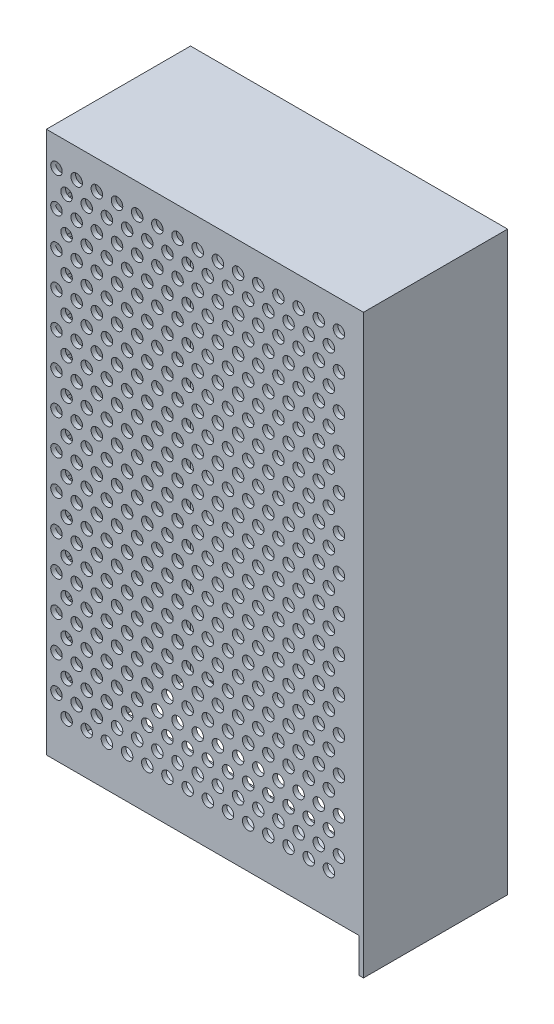
SolidWorks part; units mm, degrees
material "1060 Alloy"
ref_plane "Front Plane" through (0, 0, 0) normal (0, 0, 1) x (1, 0, 0)
ref_plane "Top Plane" through (0, 0, 0) normal (0, 1, 0) x (1, 0, 0)
ref_plane "Right Plane" through (0, 0, 0) normal (1, 0, 0) x (0, 0, -1)
sketch "Sketch1" plane through (0, 0, 0) normal (0, 0, 1) x (1, 0, 0)
  line L0 (-55, 0) -> (0, 0) construction
  line L1 (-55, 100) -> (55, 100)
  line L2 (-55, 100) -> (-55, -100)
  line L3 (-55, -100) -> (55, -100)
  line L4 (55, 100) -> (55, -100)
  line L5 (0, 0) -> (55, 0) construction
  dimension "D1" = 110
  dimension "D2" = 200
extrude "Boss-Extrude1" add sketch "Sketch1" along normal blind 50
shell "Shell1" thickness 1.6
sketch "Sketch2" plane through (0, 0, 50) normal (0, 0, 1) x (1, 0, 0)
  line L0 (-55, -100) -> (55, -100) construction
  line L1 (-53.4, -100) -> (53.4, -100)
  line L2 (-53.4, -100) -> (-53.4, -88) construction
  line L3 (-53.4, -88) -> (53.4, -88)
  line L4 (53.4, -100) -> (53.4, -88)
  line L5 (-53.4, -94) -> (-55, -94) construction
  line L6 (-55, 100) -> (-55, -100) construction
  line L7 (53.4, -94) -> (55, -94) construction
  line L8 (55, -100) -> (55, 100) construction
  line L9 (-53.4, -88) -> (-55, -88)
  line L10 (-55, -88) -> (-55, -100)
  line L11 (-55, -100) -> (-53.4, -100)
  dimension "D1" = 1.6
  dimension "D2" = 12
extrude "Cut-Extrude1" cut sketch "Sketch2" against normal up to surface (48.4 mm away) up to face at (0, -0.8, 1.6)
sketch "Sketch3" plane through (0, 0, 50) normal (0, 0, 1) x (1, 0, 0)
  line L0 (-55, 100) -> (-55, -88) construction
  line L1 (-55, -88) -> (55, -88)
  line L2 (-55, -88) -> (-55, -86.4)
  line L3 (-55, -86.4) -> (55, -86.4)
  line L4 (55, -88) -> (55, -86.4)
  line L5 (55, -100) -> (55, 100) construction
  line L6 (53.4, -88) -> (-55, -88) construction
  dimension "D1" = 1.6
extrude "Boss-Extrude2" add sketch "Sketch3" against normal blind 25
sketch "Sketch4" plane through (0, 0, 50) normal (0, 0, 1) x (1, 0, 0)
  line L0 (-55, 100) -> (-55, -88) construction
  line L1 (-42.5, 77.5) -> (7.5, 77.5) construction
  line L2 (-42.5, 77.5) -> (-42.5, 27.5) construction
  line L3 (-42.5, 27.5) -> (7.5, 27.5) construction
  line L4 (7.5, 77.5) -> (7.5, 27.5) construction
  line L5 (55, 100) -> (-55, 100) construction
  line L6 (-17.5, 77.5) -> (-17.5, 52.5) construction
  line L7 (-17.5, 52.5) -> (-17.5, 27.5) construction
  circle A0 centre (-17.5, 52.5) radius 29
  circle A1 centre (-42.5, 77.5) radius 1.5
  circle A2 centre (7.5, 27.5) radius 1.5
  dimension "D1" = 3
  dimension "D2" = 12.5
  dimension "D5" = 58
  dimension "D3" = 22.5
  dimension "D4" = 50
extrude "Cut-Extrude2" [suppressed] cut sketch "Sketch4" against normal up to surface (48.4 mm away)
sketch "Sketch5" plane through (0, 0, 0) normal (0, 0, -1) x (-1, 0, 0)
  line L0 (-55, 100) -> (55, 100) construction
  line L1 (-46, 90) -> (46, 90) construction
  line L2 (-46, 90) -> (-46, -87) construction
  line L3 (-46, -87) -> (46, -87) construction
  line L4 (46, 90) -> (46, -87) construction
  line L5 (-55, -100) -> (-55, 100) construction
  line L6 (55, 100) -> (55, -100) construction
  line L7 (55, -100) -> (-55, -100) construction
  circle A0 centre (-46, 90) radius 1.5
  circle A1 centre (46, 90) radius 1.5
  circle A2 centre (-46, -87) radius 1.5
  circle A3 centre (46, -87) radius 1.5
  dimension "D6" = 3
  dimension "D1" = 10
  dimension "D2" = 9
  dimension "D3" = 9
  dimension "D4" = 177
  dimension "D5" = 13
extrude "Cut-Extrude3" cut sketch "Sketch5" against normal up to surface (1.6 mm away) up to face at (-18.3333, -29.8667, 1.6)
sketch "Sketch6" plane through (0, 0, 50) normal (0, 0, 1) x (1, 0, 0)
  line L0 (55, 100) -> (-55, 100) construction
  line L2 (-55, 100) -> (-55, -88) construction
  line L3 (-51.5, 90) -> (-44.5, 90) construction
  line L4 (-48, 90) -> (-48, 83.9378) construction
  line L5 (-51.5, 90) -> (-48, 83.9378) construction
  line L6 (-48, 83.9378) -> (-41, 83.9378) construction
  line L7 (-51.5, 77.8756) -> (-44.5, 77.8756) construction
  line L8 (-48, 77.8756) -> (-48, 71.8135) construction
  line L9 (-51.5, 77.8756) -> (-48, 71.8135) construction
  line L10 (-48, 71.8135) -> (-41, 71.8135) construction
  line L11 (-51.5, 65.7513) -> (-44.5, 65.7513) construction
  line L12 (-48, 65.7513) -> (-48, 59.6891) construction
  line L13 (-51.5, 65.7513) -> (-48, 59.6891) construction
  line L14 (-48, 59.6891) -> (-41, 59.6891) construction
  line L15 (-51.5, 53.6269) -> (-44.5, 53.6269) construction
  line L16 (-48, 53.6269) -> (-48, 47.5648) construction
  line L17 (-51.5, 53.6269) -> (-48, 47.5648) construction
  line L18 (-48, 47.5648) -> (-41, 47.5648) construction
  line L19 (-51.5, 41.5026) -> (-44.5, 41.5026) construction
  line L20 (-48, 41.5026) -> (-48, 35.4404) construction
  line L21 (-51.5, 41.5026) -> (-48, 35.4404) construction
  line L22 (-48, 35.4404) -> (-41, 35.4404) construction
  line L23 (-51.5, 29.3782) -> (-44.5, 29.3782) construction
  line L24 (-48, 29.3782) -> (-48, 23.316) construction
  line L25 (-51.5, 29.3782) -> (-48, 23.316) construction
  line L26 (-48, 23.316) -> (-41, 23.316) construction
  line L27 (-51.5, 17.2539) -> (-44.5, 17.2539) construction
  line L28 (-48, 17.2539) -> (-48, 11.1917) construction
  line L29 (-51.5, 17.2539) -> (-48, 11.1917) construction
  line L30 (-48, 11.1917) -> (-41, 11.1917) construction
  line L31 (-51.5, 5.1295) -> (-44.5, 5.1295) construction
  line L32 (-48, 5.1295) -> (-48, -0.9327) construction
  line L33 (-51.5, 5.1295) -> (-48, -0.9327) construction
  line L34 (-48, -0.9327) -> (-41, -0.9327) construction
  line L35 (-51.5, -6.9948) -> (-44.5, -6.9948) construction
  line L36 (-48, -6.9948) -> (-48, -13.057) construction
  line L37 (-51.5, -6.9948) -> (-48, -13.057) construction
  line L38 (-48, -13.057) -> (-41, -13.057) construction
  line L39 (-51.5, -19.1192) -> (-44.5, -19.1192) construction
  line L40 (-48, -19.1192) -> (-48, -25.1814) construction
  line L41 (-51.5, -19.1192) -> (-48, -25.1814) construction
  line L42 (-48, -25.1814) -> (-41, -25.1814) construction
  line L43 (-51.5, -31.2436) -> (-44.5, -31.2436) construction
  line L44 (-48, -31.2436) -> (-48, -37.3057) construction
  line L45 (-51.5, -31.2436) -> (-48, -37.3057) construction
  line L46 (-48, -37.3057) -> (-41, -37.3057) construction
  line L47 (-51.5, -43.3679) -> (-44.5, -43.3679) construction
  line L48 (-48, -43.3679) -> (-48, -49.4301) construction
  line L49 (-51.5, -43.3679) -> (-48, -49.4301) construction
  line L50 (-48, -49.4301) -> (-41, -49.4301) construction
  line L51 (-51.5, -55.4923) -> (-44.5, -55.4923) construction
  line L52 (-48, -55.4923) -> (-48, -61.5544) construction
  line L53 (-51.5, -55.4923) -> (-48, -61.5544) construction
  line L54 (-48, -61.5544) -> (-41, -61.5544) construction
  line L55 (-51.5, -67.6166) -> (-44.5, -67.6166) construction
  line L56 (-48, -67.6166) -> (-48, -73.6788) construction
  line L57 (-51.5, -67.6166) -> (-48, -73.6788) construction
  line L58 (-48, -73.6788) -> (-41, -73.6788) construction
  line L67 (-48, 83.9378) -> (-51.5, 77.8756) construction
  line L68 (-48, 83.9378) -> (-48, 77.8756) construction
  circle A0 centre (-51.5, 90) radius 2
  circle A1 centre (-44.5, 90) radius 2
  circle A2 centre (-37.5, 90) radius 2
  circle A3 centre (-30.5, 90) radius 2
  circle A4 centre (-23.5, 90) radius 2
  circle A5 centre (-16.5, 90) radius 2
  circle A6 centre (-9.5, 90) radius 2
  circle A7 centre (-2.5, 90) radius 2
  circle A8 centre (4.5, 90) radius 2
  circle A9 centre (11.5, 90) radius 2
  circle A10 centre (18.5, 90) radius 2
  circle A11 centre (25.5, 90) radius 2
  circle A12 centre (32.5, 90) radius 2
  circle A13 centre (39.5, 90) radius 2
  circle A14 centre (46.5, 90) radius 2
  circle A15 centre (-48, 83.9378) radius 2
  circle A16 centre (-41, 83.9378) radius 2
  circle A17 centre (-34, 83.9378) radius 2
  circle A18 centre (-27, 83.9378) radius 2
  circle A19 centre (-20, 83.9378) radius 2
  circle A20 centre (-13, 83.9378) radius 2
  circle A21 centre (-6, 83.9378) radius 2
  circle A22 centre (1, 83.9378) radius 2
  circle A23 centre (8, 83.9378) radius 2
  circle A24 centre (15, 83.9378) radius 2
  circle A25 centre (22, 83.9378) radius 2
  circle A26 centre (29, 83.9378) radius 2
  circle A27 centre (36, 83.9378) radius 2
  circle A28 centre (43, 83.9378) radius 2
  circle A29 centre (-51.5, 77.8756) radius 2
  circle A30 centre (-44.5, 77.8756) radius 2
  circle A31 centre (-37.5, 77.8756) radius 2
  circle A32 centre (-30.5, 77.8756) radius 2
  circle A33 centre (-23.5, 77.8756) radius 2
  circle A34 centre (-16.5, 77.8756) radius 2
  circle A35 centre (-9.5, 77.8756) radius 2
  circle A36 centre (-2.5, 77.8756) radius 2
  circle A37 centre (4.5, 77.8756) radius 2
  circle A38 centre (11.5, 77.8756) radius 2
  circle A39 centre (18.5, 77.8756) radius 2
  circle A40 centre (25.5, 77.8756) radius 2
  circle A41 centre (32.5, 77.8756) radius 2
  circle A42 centre (39.5, 77.8756) radius 2
  circle A43 centre (46.5, 77.8756) radius 2
  circle A44 centre (-48, 71.8135) radius 2
  circle A45 centre (-41, 71.8135) radius 2
  circle A46 centre (-34, 71.8135) radius 2
  circle A47 centre (-27, 71.8135) radius 2
  circle A48 centre (-20, 71.8135) radius 2
  circle A49 centre (-13, 71.8135) radius 2
  circle A50 centre (-6, 71.8135) radius 2
  circle A51 centre (1, 71.8135) radius 2
  circle A52 centre (8, 71.8135) radius 2
  circle A53 centre (15, 71.8135) radius 2
  circle A54 centre (22, 71.8135) radius 2
  circle A55 centre (29, 71.8135) radius 2
  circle A56 centre (36, 71.8135) radius 2
  circle A57 centre (43, 71.8135) radius 2
  circle A58 centre (-51.5, 65.7513) radius 2
  circle A59 centre (-44.5, 65.7513) radius 2
  circle A60 centre (-37.5, 65.7513) radius 2
  circle A61 centre (-30.5, 65.7513) radius 2
  circle A62 centre (-23.5, 65.7513) radius 2
  circle A63 centre (-16.5, 65.7513) radius 2
  circle A64 centre (-9.5, 65.7513) radius 2
  circle A65 centre (-2.5, 65.7513) radius 2
  circle A66 centre (4.5, 65.7513) radius 2
  circle A67 centre (11.5, 65.7513) radius 2
  circle A68 centre (18.5, 65.7513) radius 2
  circle A69 centre (25.5, 65.7513) radius 2
  circle A70 centre (32.5, 65.7513) radius 2
  circle A71 centre (39.5, 65.7513) radius 2
  circle A72 centre (46.5, 65.7513) radius 2
  circle A73 centre (-48, 59.6891) radius 2
  circle A74 centre (-41, 59.6891) radius 2
  circle A75 centre (-34, 59.6891) radius 2
  circle A76 centre (-27, 59.6891) radius 2
  circle A77 centre (-20, 59.6891) radius 2
  circle A78 centre (-13, 59.6891) radius 2
  circle A79 centre (-6, 59.6891) radius 2
  circle A80 centre (1, 59.6891) radius 2
  circle A81 centre (8, 59.6891) radius 2
  circle A82 centre (15, 59.6891) radius 2
  circle A83 centre (22, 59.6891) radius 2
  circle A84 centre (29, 59.6891) radius 2
  circle A85 centre (36, 59.6891) radius 2
  circle A86 centre (43, 59.6891) radius 2
  circle A87 centre (-51.5, 53.6269) radius 2
  circle A88 centre (-44.5, 53.6269) radius 2
  circle A89 centre (-37.5, 53.6269) radius 2
  circle A90 centre (-30.5, 53.6269) radius 2
  circle A91 centre (-23.5, 53.6269) radius 2
  circle A92 centre (-16.5, 53.6269) radius 2
  circle A93 centre (-9.5, 53.6269) radius 2
  circle A94 centre (-2.5, 53.6269) radius 2
  circle A95 centre (4.5, 53.6269) radius 2
  circle A96 centre (11.5, 53.6269) radius 2
  circle A97 centre (18.5, 53.6269) radius 2
  circle A98 centre (25.5, 53.6269) radius 2
  circle A99 centre (32.5, 53.6269) radius 2
  circle A100 centre (39.5, 53.6269) radius 2
  circle A101 centre (46.5, 53.6269) radius 2
  circle A102 centre (-48, 47.5648) radius 2
  circle A103 centre (-41, 47.5648) radius 2
  circle A104 centre (-34, 47.5648) radius 2
  circle A105 centre (-27, 47.5648) radius 2
  circle A106 centre (-20, 47.5648) radius 2
  circle A107 centre (-13, 47.5648) radius 2
  circle A108 centre (-6, 47.5648) radius 2
  circle A109 centre (1, 47.5648) radius 2
  circle A110 centre (8, 47.5648) radius 2
  circle A111 centre (15, 47.5648) radius 2
  circle A112 centre (22, 47.5648) radius 2
  circle A113 centre (29, 47.5648) radius 2
  circle A114 centre (36, 47.5648) radius 2
  circle A115 centre (43, 47.5648) radius 2
  circle A116 centre (-51.5, 41.5026) radius 2
  circle A117 centre (-44.5, 41.5026) radius 2
  circle A118 centre (-37.5, 41.5026) radius 2
  circle A119 centre (-30.5, 41.5026) radius 2
  circle A120 centre (-23.5, 41.5026) radius 2
  circle A121 centre (-16.5, 41.5026) radius 2
  circle A122 centre (-9.5, 41.5026) radius 2
  circle A123 centre (-2.5, 41.5026) radius 2
  circle A124 centre (4.5, 41.5026) radius 2
  circle A125 centre (11.5, 41.5026) radius 2
  circle A126 centre (18.5, 41.5026) radius 2
  circle A127 centre (25.5, 41.5026) radius 2
  circle A128 centre (32.5, 41.5026) radius 2
  circle A129 centre (39.5, 41.5026) radius 2
  circle A130 centre (46.5, 41.5026) radius 2
  circle A131 centre (-48, 35.4404) radius 2
  circle A132 centre (-41, 35.4404) radius 2
  circle A133 centre (-34, 35.4404) radius 2
  circle A134 centre (-27, 35.4404) radius 2
  circle A135 centre (-20, 35.4404) radius 2
  circle A136 centre (-13, 35.4404) radius 2
  circle A137 centre (-6, 35.4404) radius 2
  circle A138 centre (1, 35.4404) radius 2
  circle A139 centre (8, 35.4404) radius 2
  circle A140 centre (15, 35.4404) radius 2
  circle A141 centre (22, 35.4404) radius 2
  circle A142 centre (29, 35.4404) radius 2
  circle A143 centre (36, 35.4404) radius 2
  circle A144 centre (43, 35.4404) radius 2
  circle A145 centre (-51.5, 29.3782) radius 2
  circle A146 centre (-44.5, 29.3782) radius 2
  circle A147 centre (-37.5, 29.3782) radius 2
  circle A148 centre (-30.5, 29.3782) radius 2
  circle A149 centre (-23.5, 29.3782) radius 2
  circle A150 centre (-16.5, 29.3782) radius 2
  circle A151 centre (-9.5, 29.3782) radius 2
  circle A152 centre (-2.5, 29.3782) radius 2
  circle A153 centre (4.5, 29.3782) radius 2
  circle A154 centre (11.5, 29.3782) radius 2
  circle A155 centre (18.5, 29.3782) radius 2
  circle A156 centre (25.5, 29.3782) radius 2
  circle A157 centre (32.5, 29.3782) radius 2
  circle A158 centre (39.5, 29.3782) radius 2
  circle A159 centre (46.5, 29.3782) radius 2
  circle A160 centre (-48, 23.316) radius 2
  circle A161 centre (-41, 23.316) radius 2
  circle A162 centre (-34, 23.316) radius 2
  circle A163 centre (-27, 23.316) radius 2
  circle A164 centre (-20, 23.316) radius 2
  circle A165 centre (-13, 23.316) radius 2
  circle A166 centre (-6, 23.316) radius 2
  circle A167 centre (1, 23.316) radius 2
  circle A168 centre (8, 23.316) radius 2
  circle A169 centre (15, 23.316) radius 2
  circle A170 centre (22, 23.316) radius 2
  circle A171 centre (29, 23.316) radius 2
  circle A172 centre (36, 23.316) radius 2
  circle A173 centre (43, 23.316) radius 2
  circle A174 centre (-51.5, 17.2539) radius 2
  circle A175 centre (-44.5, 17.2539) radius 2
  circle A176 centre (-37.5, 17.2539) radius 2
  circle A177 centre (-30.5, 17.2539) radius 2
  circle A178 centre (-23.5, 17.2539) radius 2
  circle A179 centre (-16.5, 17.2539) radius 2
  circle A180 centre (-9.5, 17.2539) radius 2
  circle A181 centre (-2.5, 17.2539) radius 2
  circle A182 centre (4.5, 17.2539) radius 2
  circle A183 centre (11.5, 17.2539) radius 2
  circle A184 centre (18.5, 17.2539) radius 2
  circle A185 centre (25.5, 17.2539) radius 2
  circle A186 centre (32.5, 17.2539) radius 2
  circle A187 centre (39.5, 17.2539) radius 2
  circle A188 centre (46.5, 17.2539) radius 2
  circle A189 centre (-48, 11.1917) radius 2
  circle A190 centre (-41, 11.1917) radius 2
  circle A191 centre (-34, 11.1917) radius 2
  circle A192 centre (-27, 11.1917) radius 2
  circle A193 centre (-20, 11.1917) radius 2
  circle A194 centre (-13, 11.1917) radius 2
  circle A195 centre (-6, 11.1917) radius 2
  circle A196 centre (1, 11.1917) radius 2
  circle A197 centre (8, 11.1917) radius 2
  circle A198 centre (15, 11.1917) radius 2
  circle A199 centre (22, 11.1917) radius 2
  circle A200 centre (29, 11.1917) radius 2
  circle A201 centre (36, 11.1917) radius 2
  circle A202 centre (43, 11.1917) radius 2
  circle A203 centre (-51.5, 5.1295) radius 2
  circle A204 centre (-44.5, 5.1295) radius 2
  circle A205 centre (-37.5, 5.1295) radius 2
  circle A206 centre (-30.5, 5.1295) radius 2
  circle A207 centre (-23.5, 5.1295) radius 2
  circle A208 centre (-16.5, 5.1295) radius 2
  circle A209 centre (-9.5, 5.1295) radius 2
  circle A210 centre (-2.5, 5.1295) radius 2
  circle A211 centre (4.5, 5.1295) radius 2
  circle A212 centre (11.5, 5.1295) radius 2
  circle A213 centre (18.5, 5.1295) radius 2
  circle A214 centre (25.5, 5.1295) radius 2
  circle A215 centre (32.5, 5.1295) radius 2
  circle A216 centre (39.5, 5.1295) radius 2
  circle A217 centre (46.5, 5.1295) radius 2
  circle A218 centre (-48, -0.9327) radius 2
  circle A219 centre (-41, -0.9327) radius 2
  circle A220 centre (-34, -0.9327) radius 2
  circle A221 centre (-27, -0.9327) radius 2
  circle A222 centre (-20, -0.9327) radius 2
  circle A223 centre (-13, -0.9327) radius 2
  circle A224 centre (-6, -0.9327) radius 2
  circle A225 centre (1, -0.9327) radius 2
  circle A226 centre (8, -0.9327) radius 2
  circle A227 centre (15, -0.9327) radius 2
  circle A228 centre (22, -0.9327) radius 2
  circle A229 centre (29, -0.9327) radius 2
  circle A230 centre (36, -0.9327) radius 2
  circle A231 centre (43, -0.9327) radius 2
  circle A232 centre (-51.5, -6.9948) radius 2
  circle A233 centre (-44.5, -6.9948) radius 2
  circle A234 centre (-37.5, -6.9948) radius 2
  circle A235 centre (-30.5, -6.9948) radius 2
  circle A236 centre (-23.5, -6.9948) radius 2
  circle A237 centre (-16.5, -6.9948) radius 2
  circle A238 centre (-9.5, -6.9948) radius 2
  circle A239 centre (-2.5, -6.9948) radius 2
  circle A240 centre (4.5, -6.9948) radius 2
  circle A241 centre (11.5, -6.9948) radius 2
  circle A242 centre (18.5, -6.9948) radius 2
  circle A243 centre (25.5, -6.9948) radius 2
  circle A244 centre (32.5, -6.9948) radius 2
  circle A245 centre (39.5, -6.9948) radius 2
  circle A246 centre (46.5, -6.9948) radius 2
  circle A247 centre (-48, -13.057) radius 2
  circle A248 centre (-41, -13.057) radius 2
  circle A249 centre (-34, -13.057) radius 2
  circle A250 centre (-27, -13.057) radius 2
  circle A251 centre (-20, -13.057) radius 2
  circle A252 centre (-13, -13.057) radius 2
  circle A253 centre (-6, -13.057) radius 2
  circle A254 centre (1, -13.057) radius 2
  circle A255 centre (8, -13.057) radius 2
  circle A256 centre (15, -13.057) radius 2
  circle A257 centre (22, -13.057) radius 2
  circle A258 centre (29, -13.057) radius 2
  circle A259 centre (36, -13.057) radius 2
  circle A260 centre (43, -13.057) radius 2
  circle A261 centre (-51.5, -19.1192) radius 2
  circle A262 centre (-44.5, -19.1192) radius 2
  circle A263 centre (-37.5, -19.1192) radius 2
  circle A264 centre (-30.5, -19.1192) radius 2
  circle A265 centre (-23.5, -19.1192) radius 2
  circle A266 centre (-16.5, -19.1192) radius 2
  circle A267 centre (-9.5, -19.1192) radius 2
  circle A268 centre (-2.5, -19.1192) radius 2
  circle A269 centre (4.5, -19.1192) radius 2
  circle A270 centre (11.5, -19.1192) radius 2
  circle A271 centre (18.5, -19.1192) radius 2
  circle A272 centre (25.5, -19.1192) radius 2
  circle A273 centre (32.5, -19.1192) radius 2
  circle A274 centre (39.5, -19.1192) radius 2
  circle A275 centre (46.5, -19.1192) radius 2
  circle A276 centre (-48, -25.1814) radius 2
  circle A277 centre (-41, -25.1814) radius 2
  circle A278 centre (-34, -25.1814) radius 2
  circle A279 centre (-27, -25.1814) radius 2
  circle A280 centre (-20, -25.1814) radius 2
  circle A281 centre (-13, -25.1814) radius 2
  circle A282 centre (-6, -25.1814) radius 2
  circle A283 centre (1, -25.1814) radius 2
  circle A284 centre (8, -25.1814) radius 2
  circle A285 centre (15, -25.1814) radius 2
  circle A286 centre (22, -25.1814) radius 2
  circle A287 centre (29, -25.1814) radius 2
  circle A288 centre (36, -25.1814) radius 2
  circle A289 centre (43, -25.1814) radius 2
  circle A290 centre (-51.5, -31.2436) radius 2
  circle A291 centre (-44.5, -31.2436) radius 2
  circle A292 centre (-37.5, -31.2436) radius 2
  circle A293 centre (-30.5, -31.2436) radius 2
  circle A294 centre (-23.5, -31.2436) radius 2
  circle A295 centre (-16.5, -31.2436) radius 2
  circle A296 centre (-9.5, -31.2436) radius 2
  circle A297 centre (-2.5, -31.2436) radius 2
  circle A298 centre (4.5, -31.2436) radius 2
  circle A299 centre (11.5, -31.2436) radius 2
  circle A300 centre (18.5, -31.2436) radius 2
  circle A301 centre (25.5, -31.2436) radius 2
  circle A302 centre (32.5, -31.2436) radius 2
  circle A303 centre (39.5, -31.2436) radius 2
  circle A304 centre (46.5, -31.2436) radius 2
  circle A305 centre (-48, -37.3057) radius 2
  circle A306 centre (-41, -37.3057) radius 2
  circle A307 centre (-34, -37.3057) radius 2
  circle A308 centre (-27, -37.3057) radius 2
  circle A309 centre (-20, -37.3057) radius 2
  circle A310 centre (-13, -37.3057) radius 2
  circle A311 centre (-6, -37.3057) radius 2
  circle A312 centre (1, -37.3057) radius 2
  circle A313 centre (8, -37.3057) radius 2
  circle A314 centre (15, -37.3057) radius 2
  circle A315 centre (22, -37.3057) radius 2
  circle A316 centre (29, -37.3057) radius 2
  circle A317 centre (36, -37.3057) radius 2
  circle A318 centre (43, -37.3057) radius 2
  circle A319 centre (-51.5, -43.3679) radius 2
  circle A320 centre (-44.5, -43.3679) radius 2
  circle A321 centre (-37.5, -43.3679) radius 2
  circle A322 centre (-30.5, -43.3679) radius 2
  circle A323 centre (-23.5, -43.3679) radius 2
  circle A324 centre (-16.5, -43.3679) radius 2
  circle A325 centre (-9.5, -43.3679) radius 2
  circle A326 centre (-2.5, -43.3679) radius 2
  circle A327 centre (4.5, -43.3679) radius 2
  circle A328 centre (11.5, -43.3679) radius 2
  circle A329 centre (18.5, -43.3679) radius 2
  circle A330 centre (25.5, -43.3679) radius 2
  circle A331 centre (32.5, -43.3679) radius 2
  circle A332 centre (39.5, -43.3679) radius 2
  circle A333 centre (46.5, -43.3679) radius 2
  circle A334 centre (-48, -49.4301) radius 2
  circle A335 centre (-41, -49.4301) radius 2
  circle A336 centre (-34, -49.4301) radius 2
  circle A337 centre (-27, -49.4301) radius 2
  circle A338 centre (-20, -49.4301) radius 2
  circle A339 centre (-13, -49.4301) radius 2
  circle A340 centre (-6, -49.4301) radius 2
  circle A341 centre (1, -49.4301) radius 2
  circle A342 centre (8, -49.4301) radius 2
  circle A343 centre (15, -49.4301) radius 2
  circle A344 centre (22, -49.4301) radius 2
  circle A345 centre (29, -49.4301) radius 2
  circle A346 centre (36, -49.4301) radius 2
  circle A347 centre (43, -49.4301) radius 2
  circle A348 centre (-51.5, -55.4923) radius 2
  circle A349 centre (-44.5, -55.4923) radius 2
  circle A350 centre (-37.5, -55.4923) radius 2
  circle A351 centre (-30.5, -55.4923) radius 2
  circle A352 centre (-23.5, -55.4923) radius 2
  circle A353 centre (-16.5, -55.4923) radius 2
  circle A354 centre (-9.5, -55.4923) radius 2
  circle A355 centre (-2.5, -55.4923) radius 2
  circle A356 centre (4.5, -55.4923) radius 2
  circle A357 centre (11.5, -55.4923) radius 2
  circle A358 centre (18.5, -55.4923) radius 2
  circle A359 centre (25.5, -55.4923) radius 2
  circle A360 centre (32.5, -55.4923) radius 2
  circle A361 centre (39.5, -55.4923) radius 2
  circle A362 centre (46.5, -55.4923) radius 2
  circle A363 centre (-48, -61.5544) radius 2
  circle A364 centre (-41, -61.5544) radius 2
  circle A365 centre (-34, -61.5544) radius 2
  circle A366 centre (-27, -61.5544) radius 2
  circle A367 centre (-20, -61.5544) radius 2
  circle A368 centre (-13, -61.5544) radius 2
  circle A369 centre (-6, -61.5544) radius 2
  circle A370 centre (1, -61.5544) radius 2
  circle A371 centre (8, -61.5544) radius 2
  circle A372 centre (15, -61.5544) radius 2
  circle A373 centre (22, -61.5544) radius 2
  circle A374 centre (29, -61.5544) radius 2
  circle A375 centre (36, -61.5544) radius 2
  circle A376 centre (43, -61.5544) radius 2
  circle A377 centre (-51.5, -67.6166) radius 2
  circle A378 centre (-44.5, -67.6166) radius 2
  circle A379 centre (-37.5, -67.6166) radius 2
  circle A380 centre (-30.5, -67.6166) radius 2
  circle A381 centre (-23.5, -67.6166) radius 2
  circle A382 centre (-16.5, -67.6166) radius 2
  circle A383 centre (-9.5, -67.6166) radius 2
  circle A384 centre (-2.5, -67.6166) radius 2
  circle A385 centre (4.5, -67.6166) radius 2
  circle A386 centre (11.5, -67.6166) radius 2
  circle A387 centre (18.5, -67.6166) radius 2
  circle A388 centre (25.5, -67.6166) radius 2
  circle A389 centre (32.5, -67.6166) radius 2
  circle A390 centre (39.5, -67.6166) radius 2
  circle A391 centre (46.5, -67.6166) radius 2
  circle A392 centre (-48, -73.6788) radius 2
  circle A393 centre (-41, -73.6788) radius 2
  circle A394 centre (-34, -73.6788) radius 2
  circle A395 centre (-27, -73.6788) radius 2
  circle A396 centre (-20, -73.6788) radius 2
  circle A397 centre (-13, -73.6788) radius 2
  circle A398 centre (-6, -73.6788) radius 2
  circle A399 centre (1, -73.6788) radius 2
  circle A400 centre (8, -73.6788) radius 2
  circle A401 centre (15, -73.6788) radius 2
  circle A402 centre (22, -73.6788) radius 2
  circle A403 centre (29, -73.6788) radius 2
  circle A404 centre (36, -73.6788) radius 2
  circle A405 centre (43, -73.6788) radius 2
  dimension "D1" = 4
  dimension "D2" = 10
  dimension "D3" = 3.5
  dimension "D5" = 7
  dimension "D6" = 14
  dimension "D4" = 15
  dimension "D7" = 14
extrude "Cut-Extrude4" cut sketch "Sketch6" against normal blind 10
